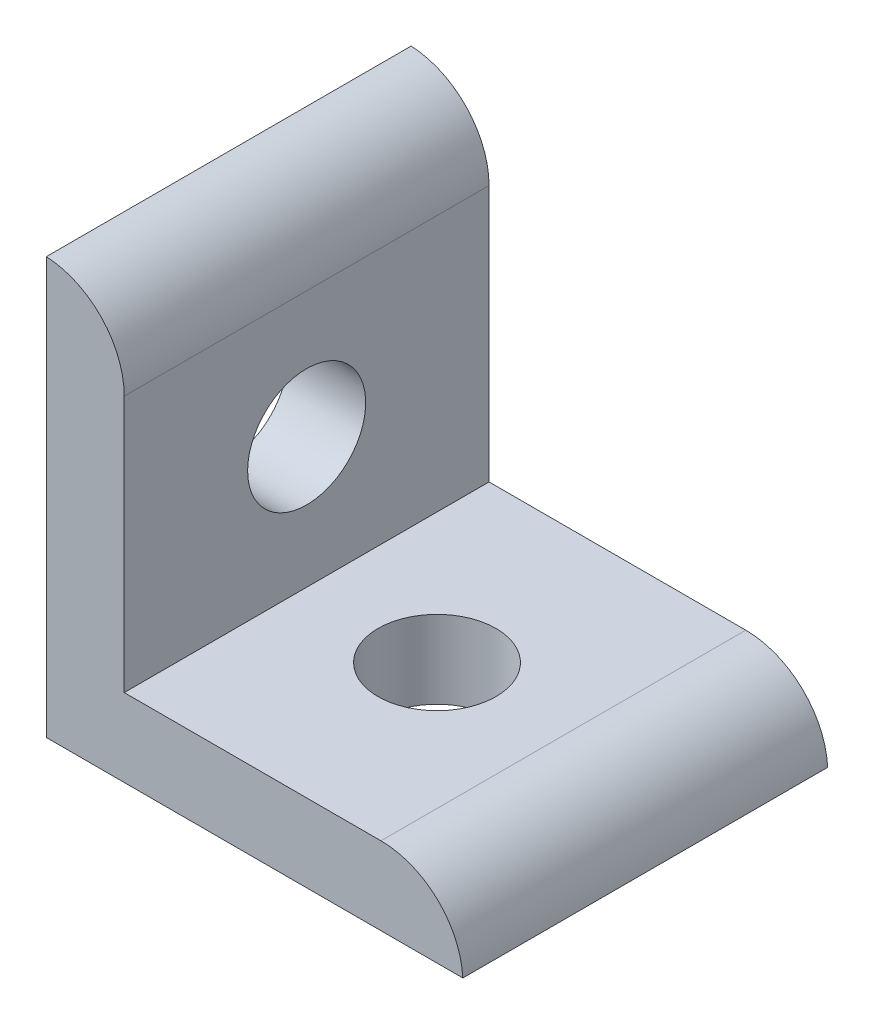
SolidWorks part; units mm, degrees
ref_plane "Front Plane" through (0, 0, 0) normal (0, 0, 1) x (1, 0, 0)
ref_plane "Top Plane" through (0, 0, 0) normal (0, 1, 0) x (1, 0, 0)
ref_plane "Right Plane" through (0, 0, 0) normal (1, 0, 0) x (0, 0, -1)
sketch "Sketch2" plane through (0, 0, 0) normal (0, 0, 1) x (1, 0, 0)
  line L0 (0, 25.4) -> (0, 0)
  line L1 (0, 0) -> (25.4, 0)
  line L2 (25.4, 0) -> (25.4, 4.75)
  line L3 (25.4, 4.75) -> (4.75, 4.75)
  line L4 (4.75, 4.75) -> (4.75, 25.4)
  line L5 (4.75, 25.4) -> (0, 25.4)
  dimension "D1" = 25.4
  dimension "D2" = 4.75
extrude "Boss-Extrude1" add sketch "Sketch2" along normal blind 22.25
fillet "Fillet1" radius 5 2 edges at (4.75, 25.4, 11.125) (25.4, 4.75, 11.125)
sketch "Sketch6" plane through (0, 0, 0) normal (0, -1, 0) x (1, 0, 0)
  line L0 (0, 0) -> (25.4, 0) construction
  line L1 (0, 22.25) -> (0, 0) construction
  circle A0 centre (12.7, 11.125) radius 3.6
  point P4 (12.7, 0)
  point P7 (0, 11.125)
  dimension "D1" = 7.2
extrude "Cut-Extrude1" cut sketch "Sketch6" against normal up to next
sketch "Sketch7" plane through (0, 0, 0) normal (-1, 0, 0) x (0, 0, 1)
  line L0 (0, 25.4) -> (0, 0) construction
  line L1 (22.25, 0) -> (0, 0) construction
  circle A0 centre (11.125, 12.7) radius 3.6
  point P5 (0, 12.7)
  point P8 (11.125, 0)
  dimension "D1" = 7.2
extrude "Cut-Extrude2" cut sketch "Sketch7" against normal up to next
